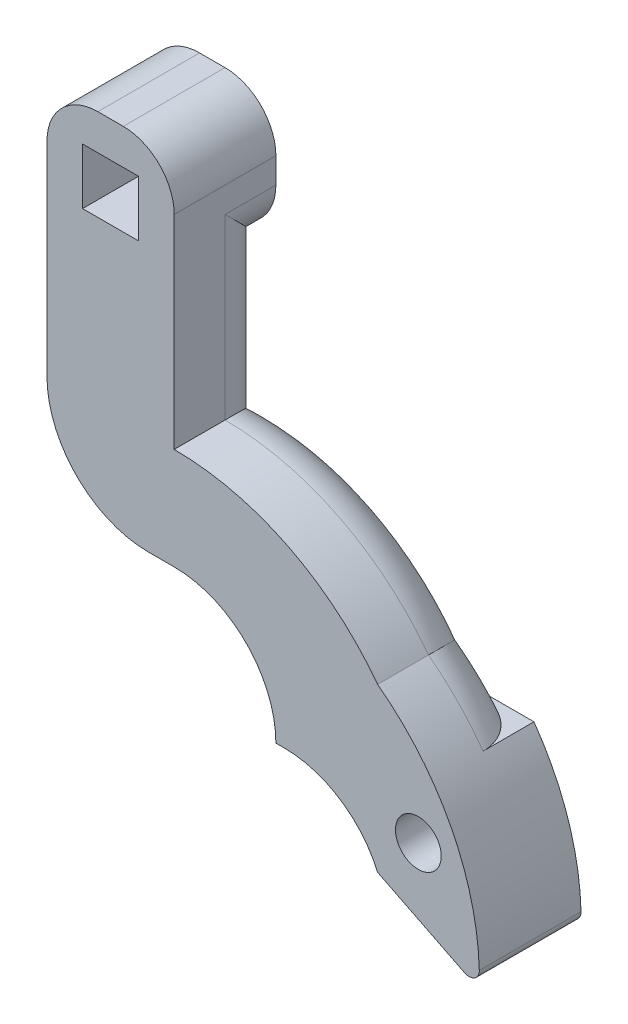
SolidWorks part; units mm, degrees
ref_plane "Front Plane" through (0, 0, 0) normal (0, 0, 1) x (1, 0, 0)
ref_plane "Top Plane" through (0, 0, 0) normal (0, 1, 0) x (1, 0, 0)
ref_plane "Right Plane" through (0, 0, 0) normal (1, 0, 0) x (0, 0, -1)
sketch "Sketch1" plane through (0, 0, 0) normal (0, 1, 0) x (1, 0, 0)
  line L1 (0, 0) -> (36.83, 0)
  line L2 (0, 0) -> (0, 16.51)
  line L3 (0, 16.51) -> (36.83, 16.51)
  line L4 (36.83, 0) -> (36.83, 16.51)
  dimension "D1" = 36.83
  dimension "D2" = 16.51
extrude "Boss-Extrude1" add sketch "Sketch1" along normal blind 6.35
hole_wizard "Ø3.0mm Dowel Hole1" positions "Sketch5" profile "Sketch4" hole size "Ø3.0" standard "ISO" end condition through all
sketch "Sketch5" plane through (0, 6.35, 0) normal (0, 1, 0) x (1, 0, 0)
  line L0 (0, 0) -> (36.83, 0) construction
  line L1 (0, 16.51) -> (0, 0) construction
  point P0 (5.08, 8.255)
  point P2 (12.7, 8.255)
  dimension "D1" = 8.255
  dimension "D2" = 5.08
  dimension "D3" = 7.62
sketch "Sketch4" plane through (5.08, 6.35, -8.255) normal (1, 0, 0) x (0, 0, 1)
  line L0 (0, 0) -> (0, 6.35)
  line L1 (0, 6.35) -> (1.5, 6.35)
  line L2 (1.5, 6.35) -> (1.5, 0)
  line L5 (1.5, 0) -> (0, 0)
  line L11 (0, -6.35) -> (0, 107.95) construction
  dimension "Thru Hole Dia." = 3
  dimension "Thru Hole Depth" = 6.35
chamfer "Chamfer1" distance 0.254 angle 45 4 edges at (12.7, 6.35, -6.755) (5.08, 6.35, -6.755) (5.08, 0, -6.755) (12.7, 0, -6.755)
fillet "Fillet2" radius 3.81 2 edges at (0, 3.175, 0) (0, 3.175, -16.51)
sketch "Sketch14" plane through (0, 0, 0) normal (0, 0, 1) x (1, 0, 0)
  line L1 (36.83, 6.35) -> (30.48, 6.35)
  line L2 (36.83, 6.35) -> (36.83, -11.43)
  line L3 (36.83, -11.43) -> (30.48, -11.43)
  line L4 (30.48, 6.35) -> (30.48, -11.43)
  dimension "D1" = 6.35
  dimension "D2" = 17.78
extrude "Boss-Extrude8" add sketch "Sketch14" along normal blind 5.08
sketch "Sketch15" plane through (0, 0, -16.51) normal (0, 0, -1) x (-1, 0, 0)
  line L1 (-36.83, 6.35) -> (-30.48, 6.35)
  line L2 (-36.83, 6.35) -> (-36.83, -11.43)
  line L3 (-36.83, -11.43) -> (-30.48, -11.43)
  line L4 (-30.48, 6.35) -> (-30.48, -11.43)
  dimension "D1" = 17.78
  dimension "D2" = 6.35
extrude "Boss-Extrude9" add sketch "Sketch15" along normal blind 5.08
sketch "Sketch16" plane through (36.83, 0, 0) normal (1, 0, 0) x (0, 0, -1)
  line L0 (0, -11.43) -> (0, 0) construction
  line L1 (-5.08, -11.43) -> (0, -11.43)
  line L2 (-5.08, -11.43) -> (-5.08, -6.35)
  line L3 (-5.08, -6.35) -> (0, -6.35)
  line L4 (0, -11.43) -> (0, -6.35)
  line L5 (21.59, 6.35) -> (21.59, -11.43) construction
  line L6 (16.51, -11.43) -> (21.59, -11.43)
  line L7 (16.51, -11.43) -> (16.51, -6.35)
  line L8 (16.51, -6.35) -> (21.59, -6.35)
  line L9 (21.59, -11.43) -> (21.59, -6.35)
  dimension "D1" = 5.08
  dimension "D2" = 5.08
extrude "Boss-Extrude10" add sketch "Sketch16" along normal blind 10.16
sketch "Sketch18" plane through (0, -11.43, 0) normal (0, -1, 0) x (1, 0, 0)
  line L0 (30.48, 0) -> (46.99, 0) construction
  line L1 (46.99, 5.08) -> (41.91, 5.08)
  line L2 (46.99, 5.08) -> (46.99, 0)
  line L3 (46.99, 0) -> (41.91, 0)
  line L4 (41.91, 5.08) -> (41.91, 0)
  line L5 (46.99, -21.59) -> (30.48, -21.59) construction
  line L6 (46.99, -16.51) -> (41.91, -16.51)
  line L7 (46.99, -16.51) -> (46.99, -21.59)
  line L8 (46.99, -21.59) -> (41.91, -21.59)
  line L9 (41.91, -16.51) -> (41.91, -21.59)
  dimension "D1" = 5.08
  dimension "D2" = 5.08
extrude "Boss-Extrude12" add sketch "Sketch18" along normal blind 5.08
sketch "Sketch19" plane through (46.99, 0, 0) normal (1, 0, 0) x (0, 0, -1)
  line L0 (0, -16.51) -> (0, -6.35) construction
  line L1 (-5.08, -16.51) -> (0, -16.51)
  line L2 (-5.08, -16.51) -> (-5.08, -11.43)
  line L3 (-5.08, -11.43) -> (0, -11.43)
  line L4 (0, -16.51) -> (0, -11.43)
  line L5 (21.59, -16.51) -> (21.59, -6.35) construction
  line L6 (16.51, -16.51) -> (21.59, -16.51)
  line L7 (16.51, -16.51) -> (16.51, -11.43)
  line L8 (16.51, -11.43) -> (21.59, -11.43)
  line L9 (21.59, -16.51) -> (21.59, -11.43)
extrude "Boss-Extrude13" add sketch "Sketch19" along normal blind 5.08
sketch "Sketch20" plane through (0, -16.51, 0) normal (0, -1, 0) x (1, 0, 0)
  line L0 (41.91, 0) -> (52.07, 0) construction
  line L1 (52.07, 5.08) -> (46.99, 5.08)
  line L2 (52.07, 5.08) -> (52.07, 0)
  line L3 (52.07, 0) -> (46.99, 0)
  line L4 (46.99, 5.08) -> (46.99, 0)
  line L5 (41.91, -21.59) -> (52.07, -21.59) construction
  line L6 (52.07, -16.51) -> (46.99, -16.51)
  line L7 (52.07, -16.51) -> (52.07, -21.59)
  line L8 (52.07, -21.59) -> (46.99, -21.59)
  line L9 (46.99, -16.51) -> (46.99, -21.59)
extrude "Boss-Extrude14" add sketch "Sketch20" along normal blind 5.588
sketch "Sketch21" plane through (0, 0, -21.59) normal (0, 0, -1) x (-1, 0, 0)
  line L0 (-46.99, -22.098) -> (-52.07, -22.098)
  line L1 (-52.07, -22.098) -> (-46.99, -19.558)
  line L2 (-46.99, -22.098) -> (-46.99, -16.51) construction
  line L3 (-46.99, -19.558) -> (-46.99, -22.098)
  dimension "D1" = 2.54
extrude "Cut-Extrude5" cut sketch "Sketch21" against normal through all
sketch "Sketch22" plane through (0, 0, -16.51) normal (0, 0, 1) x (1, 0, 0)
  line L0 (52.07, -22.098) -> (46.99, -19.558)
  line L1 (46.99, -19.558) -> (46.99, -14.224)
  line L2 (46.99, -14.224) -> (52.07, -14.224)
  line L3 (52.07, -11.43) -> (52.07, -22.098) construction
  line L4 (52.07, -14.224) -> (52.07, -22.098)
  dimension "D1" = 7.874
extrude "Boss-Extrude15" add sketch "Sketch22" along normal blind 16.51
sketch "Sketch23" plane through (46.99, 0, 0) normal (-1, 0, 0) x (0, 0, 1)
  line L0 (5.08, -19.558) -> (-21.59, -19.558) construction
  line L1 (-13.589, -19.558) -> (-2.921, -19.558)
  line L2 (-13.589, -19.558) -> (-13.589, -16.764)
  line L3 (-13.589, -16.764) -> (-2.921, -16.764)
  line L4 (-2.921, -19.558) -> (-2.921, -16.764)
  line L6 (0, -14.224) -> (-16.51, -14.224) construction
  point P6 (-8.255, -14.224)
  dimension "D1" = 2.794
  dimension "D2" = 10.668
  dimension "D3" = 5.334
extrude "Cut-Extrude6" cut sketch "Sketch23" against normal blind 16.51
fillet "Fillet3" radius 12.7 3 edges at (52.07, -11.43, -19.05) (46.99, -6.35, -19.05) (46.99, -6.35, 2.54)
fillet "Fillet4" radius 5.08 6 edges at (30.48, -11.43, -19.05) (30.48, -11.43, 2.54)
fillet "Fillet5" radius 0.508 1 edges
fillet "Fillet6" radius 2.54 20 edges at (40.4221, -12.9179, -16.51) (31.9679, -9.9421, -16.51) (40.4221, -12.9179, 0) (31.9679, -9.9421, 0) (30.48, 6.35, 2.54) (30.48, 6.35, -19.05) (36.83, 0, -8.255) (36.83, 6.35, -8.255) (48.4608, -12.7217, -16.51) (42.5096, -7.6908, -16.51) (48.4608, -12.7217, 0) (45.1165, -17.3398, 0) (45.1165, -17.3398, -16.51) (30.48, -3.175, -16.51) (30.48, -3.175, 0) (36.83, -3.175, -16.51)
sketch "Sketch24" plane through (0, 0, 0) normal (0, 0, 1) x (1, 0, 0)
  line L1 (0, 8.5066) -> (56.668, 8.5066)
  line L2 (0, 8.5066) -> (0, -31.5744)
  line L3 (0, -31.5744) -> (56.668, -31.5744)
  line L4 (56.668, 8.5066) -> (56.668, -31.5744)
extrude "Cut-Extrude7" cut sketch "Sketch24" against normal through all
sketch "Sketch25" plane through (0, 0, 5.08) normal (0, 0, 1) x (1, 0, 0)
  line L0 (34.29, 6.35) -> (33.02, 6.35) construction
  line L1 (32.258, 4.572) -> (35.052, 4.572)
  line L2 (32.258, 4.572) -> (32.258, 1.778)
  line L3 (32.258, 1.778) -> (35.052, 1.778)
  line L4 (35.052, 4.572) -> (35.052, 1.778)
  line L5 (36.83, -6.35) -> (36.83, 3.81) construction
  dimension "D1" = 2.794
  dimension "D2" = 2.794
  dimension "D3" = 1.778
  dimension "D4" = 1.778
extrude "Cut-Extrude8" cut sketch "Sketch25" against normal blind 5.08
sketch "Sketch26" plane through (0, 0, 0) normal (0, 0, -1) x (-1, 0, 0)
  line L0 (-49.7156, -14.224) -> (-46.99, -14.224) construction
  line L1 (-46.99, -15.5578) -> (-46.99, -19.558) construction
  circle A0 centre (-49.022, -17.272) radius 1.143
  dimension "D1" = 2.286
  dimension "D2" = 3.048
  dimension "D3" = 2.032
extrude "Cut-Extrude9" cut sketch "Sketch26" against normal blind 5.08
